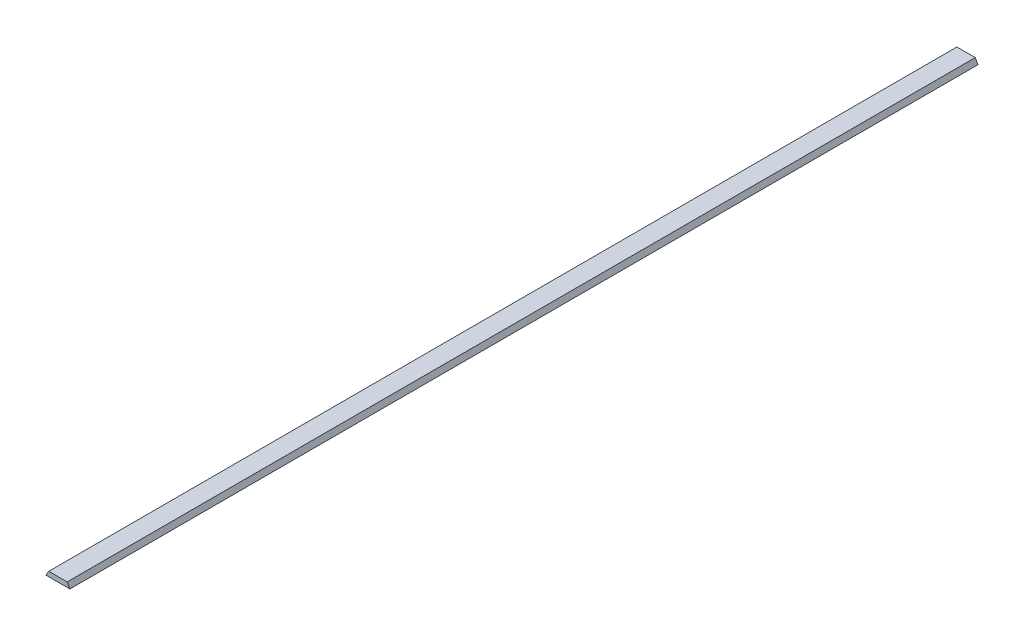
SolidWorks part; units mm, degrees
ref_plane "Front Plane" through (0, 0, 0) normal (0, 0, 1) x (1, 0, 0)
ref_plane "Top Plane" through (0, 0, 0) normal (0, 1, 0) x (1, 0, 0)
ref_plane "Right Plane" through (0, 0, 0) normal (1, 0, 0) x (0, 0, -1)
sketch "Sketch2" plane through (0, 0, 0) normal (0, 0, 1) x (1, 0, 0)
  line L1 (-1, -0.2) -> (1, -0.2)
  line L2 (-1, -0.2) -> (-1, 0.2)
  line L3 (-1, 0.2) -> (1, 0.2)
  line L4 (1, -0.2) -> (1, 0.2)
  line L5 (-1, -0.2) -> (1, 0.2) construction
  line L6 (-1, 0.2) -> (1, -0.2) construction
  point P0 (0, 0)
  dimension "D1" = 2
  dimension "D2" = 0.4
extrude "Boss-Extrude1" add sketch "Sketch2" along normal blind 76
chamfer "Chamfer1" distance 0.4 angle 30 2 edges at (1, 0.2, 38) (-1, 0.2, 38) first distance on face at (1, 0, 38) first distance on face at (-1, 0, 38)
